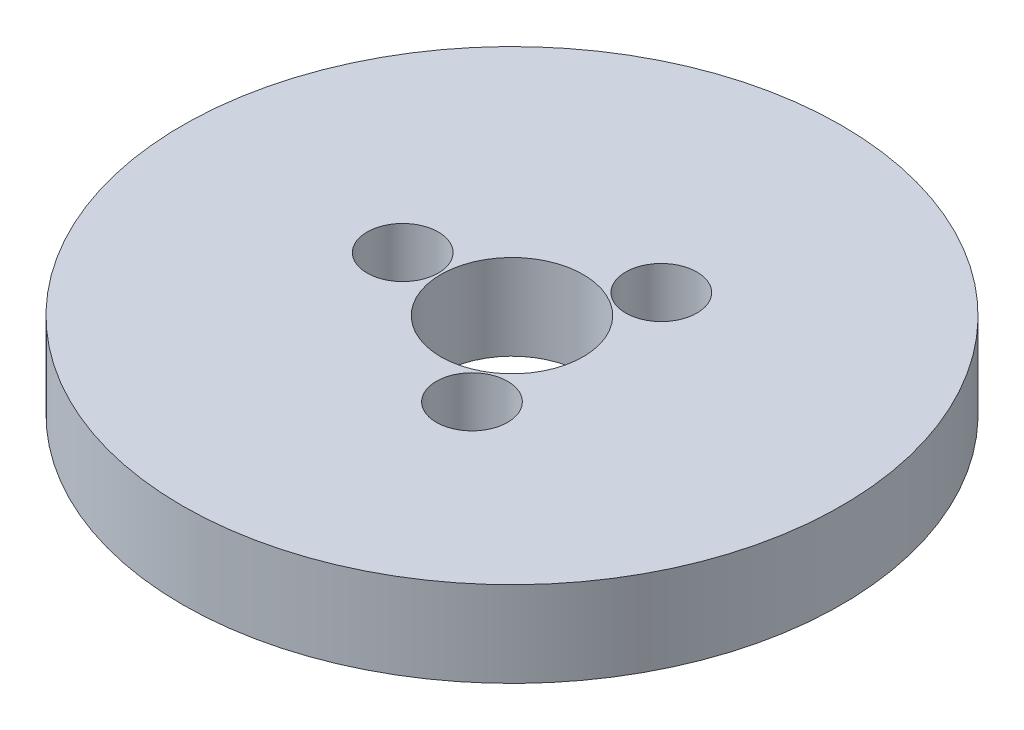
SolidWorks part; units mm, degrees
ref_plane "Front Plane" through (0, 0, 0) normal (0, 0, 1) x (1, 0, 0)
ref_plane "Top Plane" through (0, 0, 0) normal (0, 1, 0) x (1, 0, 0)
ref_plane "Right Plane" through (0, 0, 0) normal (1, 0, 0) x (0, 0, -1)
sketch "Sketch1" plane through (0, 0, 0) normal (0, 1, 0) x (1, 0, 0)
  circle A0 centre (0, 0) radius 92.5
  dimension "FLANGE_OD" = 185
extrude "Boss-Extrude1" add sketch "Sketch1" along normal blind 24
sketch "Sketch2" plane through (0, 0, 0) normal (0, 1, 0) x (1, 0, 0)
  circle A0 centre (0, 0) radius 20
  dimension "BORE_D" = 40
extrude "Cut-Extrude1" cut sketch "Sketch2" along normal through all
sketch "Sketch3" plane through (0, 24, 0) normal (0, 1, 0) x (1, 0, 0)
  circle A0 centre (0, 0) radius 30.6763 construction
  circle A1 centre (-30.6763, 0) radius 10
  dimension "BOLT_D" = 20
  dimension "BOLT_PCD" = 61.3526
extrude "Cut-Extrude2" cut sketch "Sketch3" against normal blind 20.1419
pattern_circular "CirPattern1" count 3 over 360 about axis through (0, 0, 0) along (0, 1, 0) of "Cut-Extrude2"
